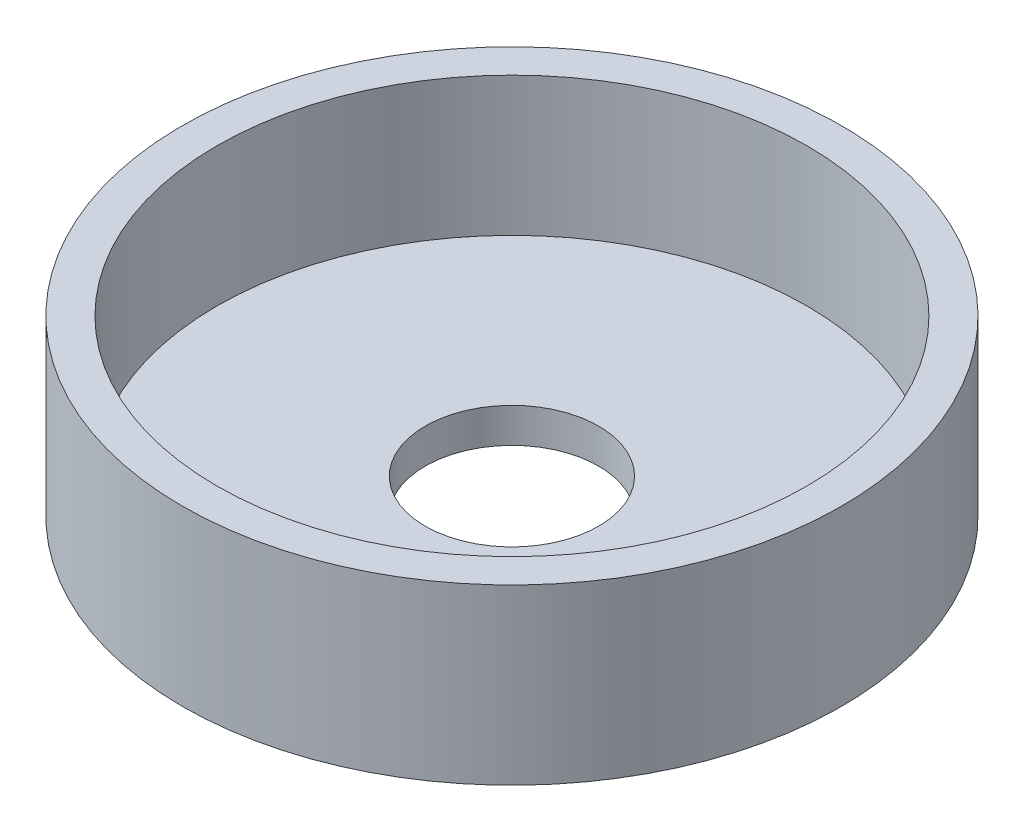
SolidWorks part; units mm, degrees
material "PLA"
ref_plane "Front Plane" through (0, 0, 0) normal (0, 0, 1) x (1, 0, 0)
ref_plane "Top Plane" through (0, 0, 0) normal (0, 1, 0) x (1, 0, 0)
ref_plane "Right Plane" through (0, 0, 0) normal (1, 0, 0) x (0, 0, -1)
sketch "Sketch1" plane through (0, 0, 0) normal (0, 1, 0) x (1, 0, 0)
  circle A0 centre (0, 0) radius 2.5
  circle A1 centre (0, 0) radius 8.5
  circle A2 centre (0, 0) radius 9.5
  dimension "D1" = 5
  dimension "D2" = 17
  dimension "D3" = 1
extrude "Boss-Extrude1" add sketch "Sketch1" along normal blind 1 contours A1 A0 | A2 A1 region at (-8.2596, 0, 0) region at (-9.2313, 0, 0)
extrude "Boss-Extrude2" add sketch "Sketch1<3>" along normal blind 5 contours A2 A1 region at (-9.2313, 0, 0)
sketch "Sketch1<3>" plane through (0, 0, 0) normal (0, 1, 0) x (1, 0, 0) same geometry as "Sketch1"
